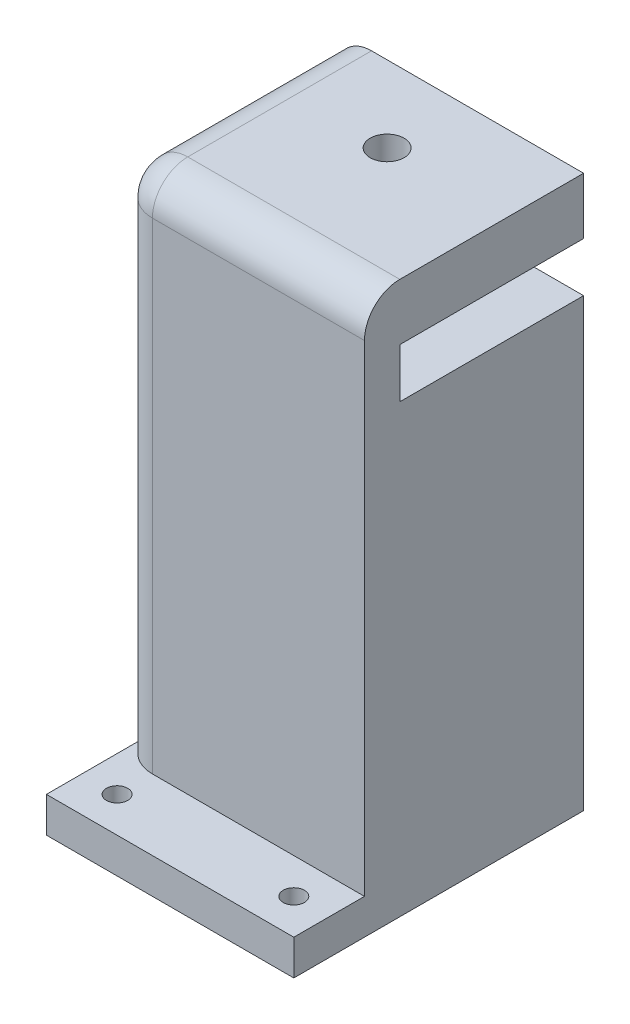
SolidWorks part; units mm, degrees
ref_plane "Front Plane" through (0, 0, 0) normal (0, 0, 1) x (1, 0, 0)
ref_plane "Top Plane" through (0, 0, 0) normal (0, 1, 0) x (1, 0, 0)
ref_plane "Right Plane" through (0, 0, 0) normal (1, 0, 0) x (0, 0, -1)
sketch "Sketch1" plane through (0, 0, 0) normal (0, 1, 0) x (1, 0, 0)
  line L1 (0, 0) -> (35, 0)
  line L2 (0, 0) -> (0, 41)
  line L3 (0, 41) -> (35, 41)
  line L4 (35, 0) -> (35, 41)
  dimension "D1" = 41
  dimension "D2" = 35
extrude "Boss-Extrude1" add sketch "Sketch1" along normal blind 5
sketch "Sketch2" plane through (0, 5, 0) normal (0, 1, 0) x (1, 0, 0)
  line L0 (0, 0) -> (35, 0) construction
  line L1 (0, 41) -> (0, 0) construction
  line L2 (35, 0) -> (35, 41) construction
  circle A0 centre (5, 5) radius 1.5
  circle A1 centre (30, 5) radius 1.5
  dimension "D1" = 5
  dimension "D3" = 5
  dimension "D2" = 5
  dimension "D4" = 5
extrude "Cut-Extrude1" cut sketch "Sketch2" against normal blind 5
sketch "Sketch3" plane through (0, 5, 0) normal (0, 1, 0) x (1, 0, 0)
  line L0 (35, 0) -> (35, 41) construction
  line L1 (0, 41) -> (35, 41)
  line L2 (0, 41) -> (0, 10)
  line L3 (0, 10) -> (35, 10)
  line L4 (35, 41) -> (35, 10)
  line L5 (0, 0) -> (35, 0) construction
  dimension "D1" = 10
extrude "Boss-Extrude2" add sketch "Sketch3" along normal blind 73.1
sketch "Sketch4" plane through (35, 0, 0) normal (1, 0, 0) x (0, 0, -1)
  line L0 (41, 78.1) -> (41, 0) construction
  line L1 (15, 70.1) -> (41, 70.1)
  line L2 (15, 70.1) -> (15, 63.1)
  line L3 (15, 63.1) -> (41, 63.1)
  line L4 (41, 70.1) -> (41, 63.1)
  line L5 (0, 0) -> (41, 0) construction
  dimension "D1" = 7
  dimension "D2" = 63.1
  dimension "D3" = 26
extrude "Cut-Extrude2" cut sketch "Sketch4" against normal blind 30
sketch "Sketch5" plane through (0, 78.1, 0) normal (0, 1, 0) x (1, 0, 0)
  line L0 (0, 41) -> (0, 10) construction
  circle A0 centre (18, 30.2021) radius 2.4
  dimension "D1" = 18
extrude "Cut-Extrude3" cut sketch "Sketch5" against normal blind 8
fillet "Fillet1" radius 5 1 edges at (0, 78.1, -25.5)
fillet "Fillet2" radius 5 3 edges at (0, 39.05, -10) (1.4645, 76.6355, -10) (20, 78.1, -10)
